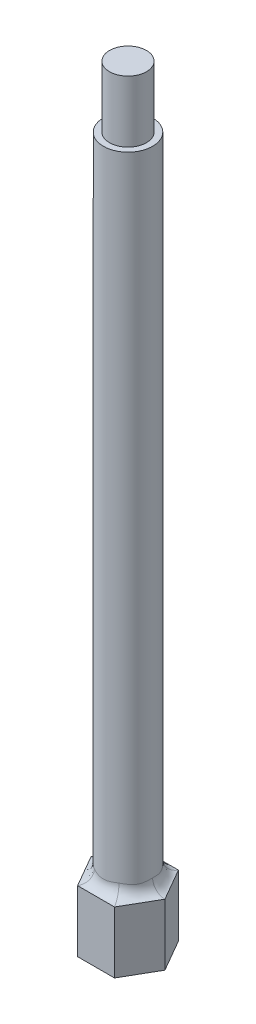
SolidWorks part; units mm, degrees
ref_plane "Front Plane" through (0, 0, 0) normal (0, 0, 1) x (1, 0, 0)
ref_plane "Top Plane" through (0, 0, 0) normal (0, 1, 0) x (1, 0, 0)
ref_plane "Right Plane" through (0, 0, 0) normal (1, 0, 0) x (0, 0, -1)
sketch "Sketch1" plane through (0, 0, 0) normal (0, 1, 0) x (1, 0, 0)
  line L1 (6, 0) -> (3, 5.1962)
  line L2 (3, 5.1962) -> (-3, 5.1962)
  line L3 (-3, 5.1962) -> (-6, 0)
  line L4 (-6, 0) -> (-3, -5.1962)
  line L5 (-3, -5.1962) -> (3, -5.1962)
  line L6 (3, -5.1962) -> (6, 0)
  circle A0 centre (0, 0) radius 5.1962 construction
  dimension "D1" = 6
extrude "Boss-Extrude1" add sketch "Sketch1" along normal blind 10
sketch "Sketch2" plane through (0, 0, 0) normal (0, -1, 0) x (-1, 0, 0)
  circle A0 centre (0, 0) radius 3
extrude "Cut-Extrude1" cut sketch "Sketch2" against normal blind 8
chamfer "Chamfer1" distance 0.5 angle 45 1 edges at (0, 0, -3)
sketch "Sketch3" plane through (0, 10, 0) normal (0, 1, 0) x (1, 0, 0)
  circle A0 centre (0, 0) radius 4
extrude "Boss-Extrude2" add sketch "Sketch3" along normal blind 115
fillet "Fillet3" radius 2 1 edges at (0, 10, 4)
sketch "Sketch4" plane through (0, 125, 0) normal (0, 1, 0) x (1, 0, 0)
  circle A0 centre (0, 0) radius 3
  circle A1 centre (0, 0) radius 4
extrude "Cut-Extrude2" cut sketch "Sketch4" against normal blind 10
